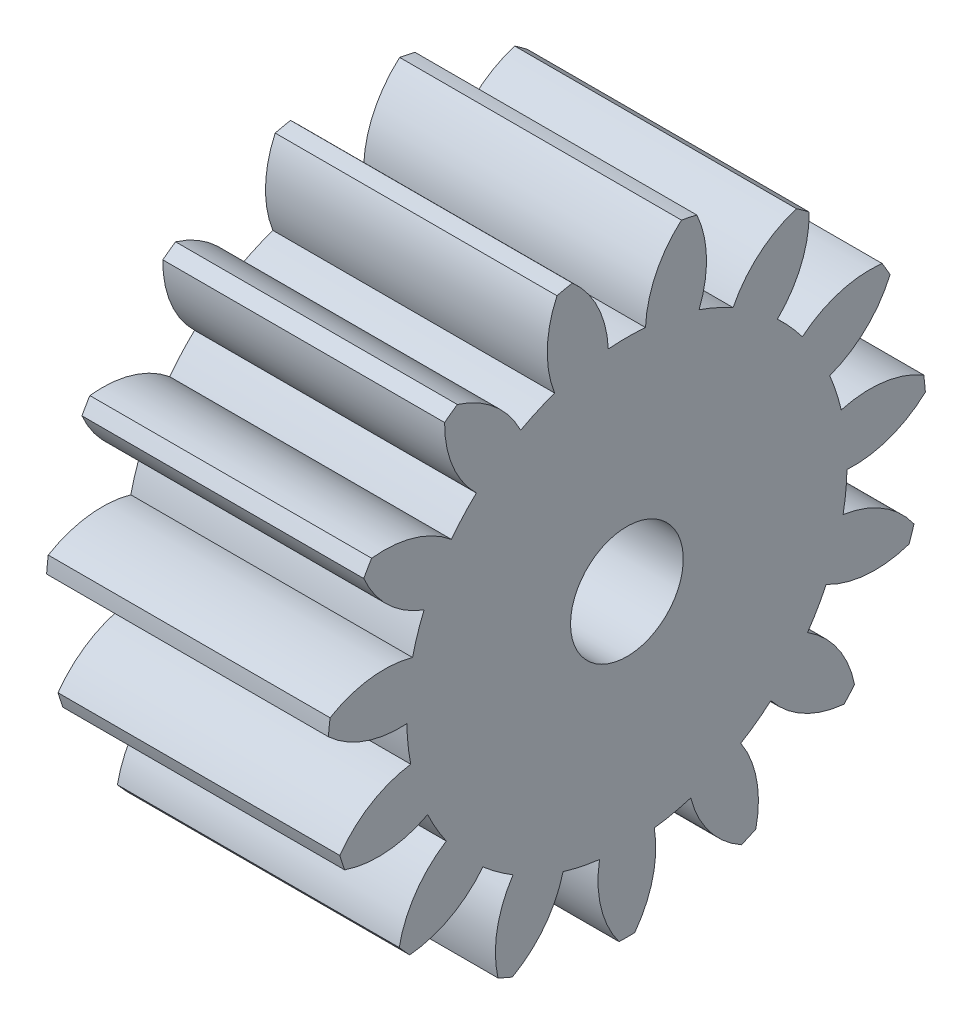
SolidWorks part; units mm, degrees
ref_plane "Plane1" through (0, 0, 0) normal (0, 0, 1) x (1, 0, 0)
ref_plane "Plane2" through (0, 0, 0) normal (0, 1, 0) x (1, 0, 0)
ref_plane "Plane3" through (0, 0, 0) normal (1, 0, 0) x (0, 0, -1)
sketch "HoldingSke" plane through (0, 0, 0) normal (0, 1, 0) x (1, 0, 0)
  line L0 (0, 0) -> (0.7727, -0.2071)
  line L1 (-15, 0) -> (100, 0) construction
  line L2 (0, 0) -> (-2.1039, 2.3779)
  line L3 (0, 0) -> (-11.863, 4.5341)
  line L4 (0, 0) -> (8.3417, 2.2352)
  line L5 (0, 0) -> (-46.8476, -17.4728)
  line L6 (0, 0) -> (-8.2896, -5.593)
  line L7 (-2.1039, 2.3779) -> (8.6586, 51.2059)
  line L8 (-76.2, 54.61) -> (-75.5, 54.61)
  line L9 (-71.009, 38.7566) -> (-53.1078, 45.2721)
  line L10 (-76.2, 71.12) -> (104.1128, 71.12)
  line L11 (0, 0) -> (-10, 0)
  line L12 (-76.2, 101.6) -> (-76.155, 101.6)
  line L13 (24.9733, 27.94) -> (52.9518, 28.4284)
  line L14 (24.9733, 27.94) -> (24.9743, 27.94)
  line L15 (24.9733, 27.94) -> (100.4006, 29.5858)
  line L16 (-63.627, -1.25) -> (-12.827, -1.25)
  circle A0 centre (0, 0) radius 2
  circle A1 centre (0, 0) radius 7.8115
  circle A2 centre (0, 0) radius 37.5
  circle A3 centre (0, 0) radius 2
  dimension "Num_teeth" = 15
  dimension "Pitch_radius" = 180.3128
  dimension "Width" = 10
  dimension "Thickness" = 10
sketch "BasProSke" plane through (0, 0, 0) normal (0, 1, 0) x (1, 0, 0)
  line L0 (-10, 0) -> (60, 0) construction
  line L1 (0, 0) -> (0, 10.625)
  line L2 (0, 0) -> (10, 0)
  line L3 (10, 0) -> (10, 10.625)
  line L4 (10, 10.625) -> (0, 10.625)
  dimension "Thickness" = 10
  dimension "Diameter" = 21.25
revolve "Base-Revolve" add sketch "BasProSke" angle 360 about L0
sketch "TooCutSke" plane through (0, 0, 0) normal (1, 0, 0) x (0, 0, -1)
  line L1 (0, 0) -> (0, 107) construction
  line L2 (0, 0) -> (-1.0586, 9.315) construction
  line L3 (0, 0) -> (-3.8803, 18.2553) construction
  line L4 (-1.0586, 9.315) -> (-1.9401, 9.1277) construction
  arc A0 (0.6608, 7.7835) -> (-0.6608, 7.7835) centre (0, 0) ccw
  arc A1 (1.9597, 10.4686) -> (-1.9597, 10.4686) centre (0, 0) ccw
  circle A2 centre (0, 0) radius 9.375 construction
  circle A3 centre (0, 0) radius 8.8096 construction
  arc A4 (-0.6608, 7.7835) -> (-1.9597, 10.4686) centre (-4.4076, 7.6277) ccw
  arc A5 (1.9597, 10.4686) -> (0.6608, 7.7835) centre (4.4076, 7.6277) ccw
extrude "ToothCut" cut sketch "TooCutSke" along normal through all
fillet "Breaks" [suppressed] radius 0.025 tangent propagation no
fillet "RootFillets" [suppressed] radius 0.3135
pattern_circular "TeethCuts" count 15 every 24 about axis through (-10, 0, 0) along (1, 0, 0) of "ToothCut", "RootFillets", "Breaks"
sketch "HubNeaOneSke" plane through (0, 0, 0) normal (-1, 0, 0) x (0, 0, 1)
  circle A0 centre (0, 0) radius 7.8115
  dimension "Diameter" = 15.623
extrude "HubNearOne" [suppressed] add sketch "HubNeaOneSke" along normal blind 40.0001
sketch "HubNeaBotSke" plane through (0, 0, 0) normal (-1, 0, 0) x (0, 0, 1)
  circle A0 centre (0, 0) radius 7.8115
  dimension "Diameter" = 15.623
extrude "HubNearBoth" [suppressed] add sketch "HubNeaBotSke" along normal blind 20
ref_plane "FarPln" through (10, 0, 0) normal (1, 0, 0) x (0, 0, -1)
sketch "HubFarSke" plane through (10, 0, 0) normal (1, 0, 0) x (0, 0, -1)
  circle A0 centre (0, 0) radius 7.8115
  dimension "Diameter" = 15.623
extrude "HubFar" [suppressed] add sketch "HubFarSke" along normal blind 20
sketch "BorSke" plane through (0, 0, 0) normal (1, 0, 0) x (0, 0, -1)
  circle A0 centre (0, 0) radius 2
  dimension "Diameter" = 4
extrude "Bore" cut sketch "BorSke" along normal mid plane 100.0001
sketch "KeySke" plane through (0, 0, 0) normal (1, 0, 0) x (0, 0, -1)
  line L0 (-0.8, 0) -> (-0.8, 2.7)
  line L1 (-0.8, 2.7) -> (0.8, 2.7)
  line L2 (0.8, 2.7) -> (0.8, 0)
  line L3 (0, 0) -> (0, 34) construction
  line L4 (-0.8, 0) -> (0.8, 0)
  dimension "Width" = 1.6
extrude "Keyway" [suppressed] cut sketch "KeySke" along normal mid plane 100.0001
pattern_circular "Keyway2" [suppressed] count 2 every 90 about axis through (-10, 0, 0) along (1, 0, 0) reverse direction yes
sketch "Sketch1" plane through (10, 0, 0) normal (1, 0, 0) x (0, 0, -1)
equation "' \"Module@HoldingSke\" = 6.35"
equation "' \"Num_teeth@HoldingSke\" = 12"
equation "' \"Ap@HoldingSke\" =  20"
equation "' \"Ap@HoldingSke\" = 20"
equation "' \"Width@HoldingSke\" = 0.5 * 25.4"
equation "' \"Hub_dia@HoldingSke\"= 1 * 25.4"
equation "' \"Hub_dia@HoldingSke\" = 1 * 25.4"
equation "' \"Overall_len@HoldingSke\" = 1.0 * 25.4"
equation "' \"Bore@HoldingSke\" = 0.75 * 25.4"
equation "' \"T_dim@HoldingSke\" = 0.1 * 25.4"
equation "' \"Width@KeySke\" = 0.25 * 25.4"
equation "' \"Show_teeth@HoldingSke\" = 13"
equation "' \"Backlash@HoldingSke\" = 0.009 * 25.4"
equation "' \"Addendum_fac@HoldingSke\" = 1.0"
equation "' \"Dedendum_fac@HoldingSke\" = 1.25"
equation "' \"Dedendum_add@HoldingSke\" = 0.00005 * 25.4"
equation "' \"Clearance_fac@HoldingSke\" = 0.25"
equation "\"Pitch@HoldingSke\" = 1 / \"Module@HoldingSke\""
equation "\"Overcut_dia@TooCutSke\" = (\"Num_teeth@HoldingSke\" + 2 * \"Addendum_fac@HoldingSke\") / \"Pitch@HoldingSke\" + 0.002 * 25.4"
equation "\"Pitch_dia@TooCutSke\" = \"Num_teeth@HoldingSke\" / \"Pitch@HoldingSke\""
equation "\"Base_dia@TooCutSke\" = \"Num_teeth@HoldingSke\" / \"Pitch@HoldingSke\" * cos((\"Ap@HoldingSke\"  * 3.14159265 / 180))"
equation "\"Root_dia@TooCutSke\" = (\"Num_teeth@HoldingSke\" + 2) / \"Pitch@HoldingSke\" - 2 * (\"Addendum_fac@HoldingSke\" + \"Dedendum_fac@HoldingSke\") / \"Pitch@HoldingSke\" - \"Dedendum_add@HoldingSke\" * 2"
equation "\"Half_ang@TooCutSke\" = 180 / \"Num_teeth@HoldingSke\""
equation "\"Half_CT@TooCutSke\" = \"Num_teeth@HoldingSke\" / \"Pitch@HoldingSke\" * sin((3.14159265 / 2 / \"Num_teeth@HoldingSke\")) / 2 - 7 * \"Backlash@HoldingSke\" / 4"
equation "\"Flank_rad@TooCutSke\" = \"Num_teeth@HoldingSke\" / \"Pitch@HoldingSke\" / 5"
equation "\"Radius@RootFillets\" = \"Clearance_fac@HoldingSke\" / \"Pitch@HoldingSke\" + \"Dedendum_add@HoldingSke\""
equation "\"Break_rad@Breaks\" = 0.02 / \"Pitch@HoldingSke\""
equation "\"Thickness@HoldingSke\" = \"Width@HoldingSke\""
equation "\"OAL@HoldingSke\" = \"Thickness@HoldingSke\""
equation "\"MHD@HoldingSke\" = (\"Num_teeth@HoldingSke\" + 2) / \"Pitch@HoldingSke\" - 2 * (\"Addendum_fac@HoldingSke\" + \"Dedendum_fac@HoldingSke\")  / \"Pitch@HoldingSke\" - \"Dedendum_add@HoldingSke\" * 2"
equation "\"MBD@HoldingSke\" = (\"Num_teeth@HoldingSke\" + 2) / \"Pitch@HoldingSke\" - 2 * (\"Addendum_fac@HoldingSke\" + \"Dedendum_fac@HoldingSke\")  / \"Pitch@HoldingSke\" - \"Dedendum_add@HoldingSke\" * 2 - 0.002 * 25.4"
equation "\"MHD@HoldingSke\" = ((sgn( \"MHD@HoldingSke\" - \"Hub_dia@HoldingSke\" )-1)*( \"MHD@HoldingSke\" - \"Hub_dia@HoldingSke\" ))/-2+ \"Hub_dia@HoldingSke\""
equation "\"MBD@HoldingSke\" = ((sgn( \"MBD@HoldingSke\" - \"Bore@HoldingSke\" )-1)*( \"MBD@HoldingSke\" - \"Bore@HoldingSke\" ))/-2+ \"Bore@HoldingSke\""
equation "\"OAL@HoldingSke\" = ((sgn( \"OAL@HoldingSke\" - \"Overall_len@HoldingSke\" )+1)*( \"OAL@HoldingSke\" - \"Overall_len@HoldingSke\" ))/2 + \"Overall_len@HoldingSke\" + 0.000002 * 25.4"
equation "\"Num_teeth@TeethCuts\" = int( \"Show_teeth@HoldingSke\" ) + 1"
equation "\"Num_teeth@TeethCuts\" = ((sgn( \"Num_teeth@TeethCuts\" - \"Num_teeth@HoldingSke\" )-1)*( \"Num_teeth@TeethCuts\" - \"Num_teeth@HoldingSke\" ))/-2+ \"Num_teeth@HoldingSke\""
equation "\"Num_teeth@TeethCuts\" = ((sgn( \"Num_teeth@TeethCuts\" - 2.0)+1)*( \"Num_teeth@TeethCuts\" - 2.0))/2 +2.0"
equation "\"Angle@TeethCuts\" = 360.0 / \"Num_teeth@HoldingSke\""
equation "\"Diameter@BasProSke\" = (\"Num_teeth@HoldingSke\" + 2 * \"Addendum_fac@HoldingSke\") / \"Pitch@HoldingSke\""
equation "\"Thickness@BasProSke\"  = \"Thickness@HoldingSke\""
equation "' \"Fillet_rad@BasProSke\" =  \"Thickness@HoldingSke\" * 0.05"
equation "' \"Fillet_rad@BasProSke\" = \"Thickness@HoldingSke\" * 0.05"
equation "\"MHD@HoldingSke\" = ((sgn( \"MHD@HoldingSke\" - \"Root_dia@TooCutSke\" )-1)*( \"MHD@HoldingSke\" - \"Root_dia@TooCutSke\" ))/-2+ \"Root_dia@TooCutSke\""
equation "\"Diameter@HubNeaOneSke\" = \"MHD@HoldingSke\""
equation "\"Length@HubNearOne\" = \"OAL@HoldingSke\" - \"Thickness@BasProSke\""
equation "\"Diameter@HubNeaBotSke\" = \"MHD@HoldingSke\""
equation "\"Length@HubNearBoth\" = ( \"OAL@HoldingSke\" - \"Thickness@BasProSke\" ) / 2.0"
equation "\"Thickness@FarPln\" = \"Thickness@BasProSke\""
equation "\"Diameter@HubFarSke\" = \"MHD@HoldingSke\""
equation "\"Length@HubFar\" = ( \"OAL@HoldingSke\" - \"Thickness@BasProSke\" ) / 2.0"
equation "\"Diameter@BorSke\" = \"MBD@HoldingSke\""
equation "\"D1@Bore\" = \"OAL@HoldingSke\" * 2.0"
equation "\"D1@Keyway\" = \"OAL@HoldingSke\" * 2.0"
equation "\"Offset@KeySke\" = \"T_dim@HoldingSke\" + \"MBD@HoldingSke\" / 2.0"
